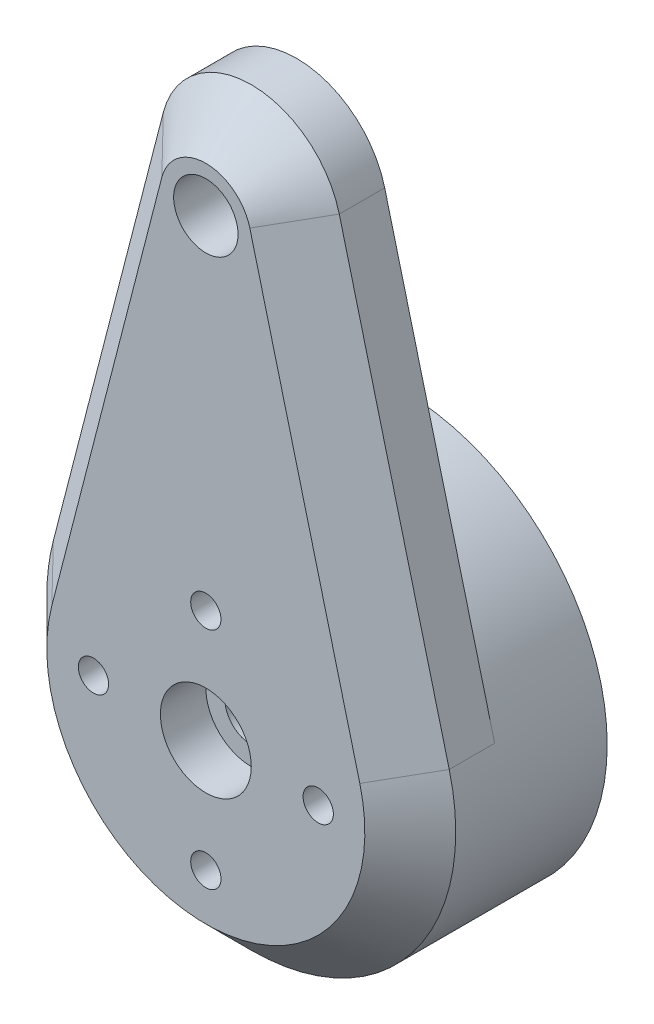
SolidWorks part; units mm, degrees
ref_plane "Front Plane" through (0, 0, 0) normal (0, 0, 1) x (1, 0, 0)
ref_plane "Top Plane" through (0, 0, 0) normal (0, 1, 0) x (1, 0, 0)
ref_plane "Right Plane" through (0, 0, 0) normal (1, 0, 0) x (0, 0, -1)
sketch "Sketch1" plane through (0, 0, 0) normal (0, 0, 1) x (1, 0, 0)
  line L0 (0, 0) -> (0, 30) construction
  line L1 (-13.0713, 3.375) -> (-5.8095, 31.5)
  line L2 (5.8095, 31.5) -> (13.0713, 3.375)
  arc A0 (-13.0713, 3.375) -> (13.0713, 3.375) centre (0, 0) ccw
  arc A1 (5.8095, 31.5) -> (-5.8095, 31.5) centre (0, 30) ccw
  circle A2 centre (0, 30) radius 2.125
  circle A3 centre (0, 0) radius 10
  circle A4 centre (0, 0) radius 1.625
  dimension "D1" = 27
  dimension "D3" = 12
  dimension "D4" = 4.25
  dimension "D5" = 20
  dimension "D6" = 3.25
  dimension "D2" = 30
extrude "Boss-Extrude1" add sketch "Sketch1" along normal blind 6 contours A3 | L2 A1 L1 A0 A3 A2 | A4 region at (0, 12.4311, 0) region at (-9.7172, 0, 0) region at (0, 0, 0)
sketch "Sketch4" plane through (0, 0, 0) normal (0, 0, -1) x (-1, 0, 0)
  circle A4 centre (0, 0) radius 13.5
  arc A5 (-13.0713, 3.375) -> (13.0713, 3.375) centre (0, 0) ccw construction
extrude "Boss-Extrude2" add sketch "Sketch4" along normal blind 7
sketch "Sketch6" plane through (0, 0, -7) normal (0, 0, -1) x (-1, 0, 0)
  circle A0 centre (0, 0) radius 11
  dimension "D1" = 22
extrude "Cut-Extrude4" cut sketch "Sketch6" against normal blind 4
sketch "Sketch5" plane through (0, 0, -3) normal (0, 0, -1) x (-1, 0, 0)
  line L0 (0, 0) -> (7.42, 0) construction
  circle A0 centre (7.42, 0) radius 1
  circle A1 centre (0, -7.42) radius 1
  circle A2 centre (-7.42, 0) radius 1
  circle A3 centre (0, 7.42) radius 1
  circle A4 centre (0, 0) radius 7.42 construction
  circle A5 centre (0, 0) radius 1.75
  point P5 (0, 0)
  point P12 (0, 0)
  point P14 (0, 0)
  dimension "D2" = 2
  dimension "D1" = 14.84
  dimension "D4" = 3.5
  dimension "D3" = 4
extrude "Cut-Extrude2" cut sketch "Sketch5" against normal through all
chamfer "Chamfer1" distance 3 angle 45 4 edges at (0, -13.5, 6) (-9.4404, 17.4375, 6) (0, 36, 6) (9.4404, 17.4375, 6)
sketch "Sketch7" plane through (0, 0, 6) normal (0, 0, 1) x (1, 0, 0)
  circle A0 centre (0, 0) radius 3
  dimension "D1" = 6
extrude "Cut-Extrude5" cut sketch "Sketch7" against normal blind 3
